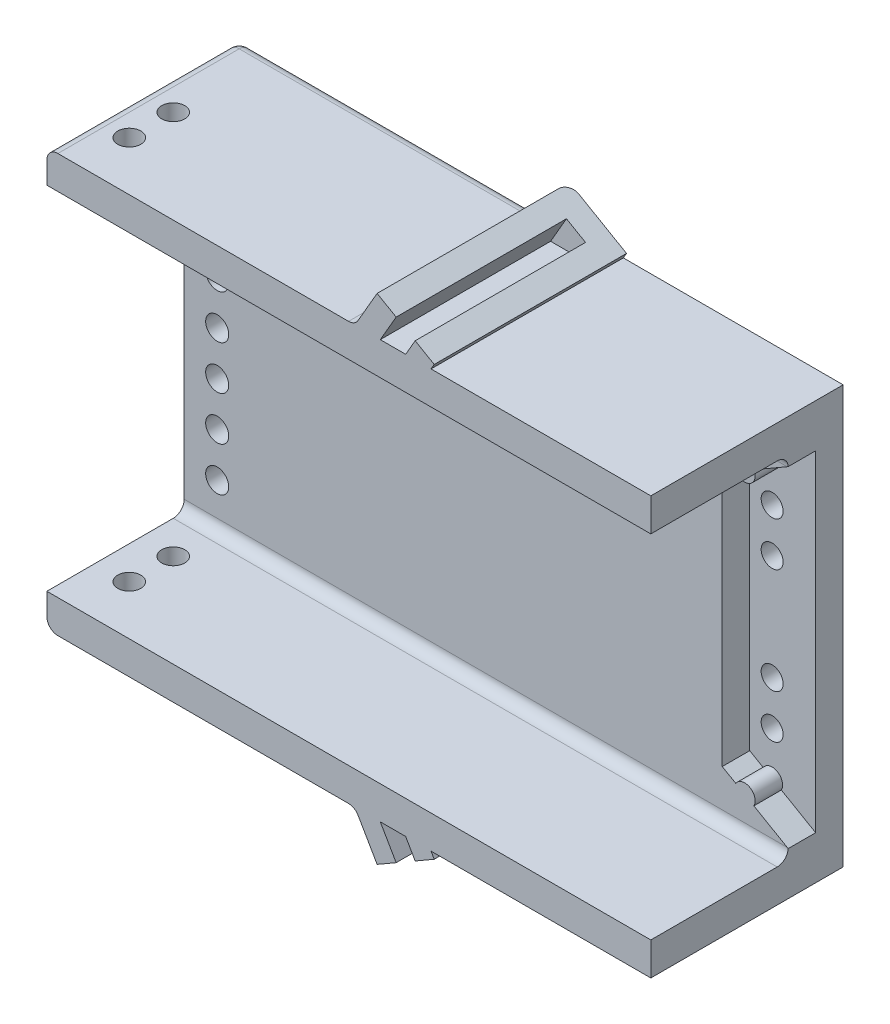
SolidWorks part; units mm, degrees
material "ABS"
ref_plane "前基準面" through (0, 0, 0) normal (0, 0, 1) x (1, 0, 0)
ref_plane "上基準面" through (0, 0, 0) normal (0, 1, 0) x (1, 0, 0)
ref_plane "右基準面" through (0, 0, 0) normal (1, 0, 0) x (0, 0, -1)
sketch "草圖2" plane through (0, 0, 0) normal (0, 0, 1) x (1, 0, 0)
  line L1 (-42.4346, 62.0442) -> (67.4854, 62.0442)
  line L2 (-42.4346, 62.0442) -> (-42.4346, -13.9558)
  line L3 (-42.4346, -13.9558) -> (67.4854, -13.9558)
  line L4 (67.4854, 62.0442) -> (67.4854, -13.9558)
  dimension "D1" = 109.92
  dimension "D2" = 76
extrude "填料-伸長1" add sketch "草圖2" along normal blind 10
sketch "草圖3" plane through (0, 0, 10) normal (0, 0, 1) x (1, 0, 0)
  line L0 (67.4854, 54.1442) -> (67.4854, -6.0558)
  line L1 (67.4854, -13.9558) -> (67.4854, 62.0442) construction
  line L2 (67.4854, 62.0442) -> (-42.4346, 62.0442) construction
  line L3 (67.4854, 54.1442) -> (55.4854, 47.2142)
  line L4 (55.4854, 47.2142) -> (55.4854, 0.8742)
  line L5 (55.4854, 0.8742) -> (67.4854, -6.0558)
  circle A0 centre (59.5654, 49.6442) radius 1.9
  circle A1 centre (59.5654, -1.5558) radius 1.9
  line M6 (67.4854, -13.9558) -> (67.4854, 62.0442)
  dimension "D7" = 7.92
  dimension "D8" = 7.92
  dimension "D9" = 3.8
  dimension "D10" = 3.8
  dimension "D12" = 12.4
  dimension "D1" = 60.2
  dimension "D2" = 7.9
  dimension "D3" = 12
  dimension "D4" = 12
  dimension "D5" = 46.34
  dimension "D6" = 6.93
  dimension "D11" = 51.2
extrude "除料-伸長1" cut sketch "草圖3" against normal blind 5 contours A1 L5 L3 A0 L4 M6
sketch "草圖4" plane through (0, 0, 5) normal (0, 0, 1) x (1, 0, 0)
  line L0 (67.4854, -6.0558) -> (67.4854, 54.1442) construction
  circle A0 centre (59.5654, 41.6442) radius 2
  arc A1 (57.953, 48.6392) -> (61.2418, 50.5385) centre (59.5654, 49.6442) ccw construction
  circle A2 centre (59.5654, 33.6442) radius 2
  circle A3 centre (59.5654, 6.4442) radius 2
  arc A4 (61.2418, -2.4501) -> (57.953, -0.5508) centre (59.5654, -1.5558) ccw construction
  circle A5 centre (59.5654, 14.4442) radius 2
  dimension "D1" = 7.92
  dimension "D2" = 8
  dimension "D3" = 4
  dimension "D5" = 4
  dimension "D6" = 7.92
  dimension "D7" = 8
  dimension "D4" = 2
  dimension "D8" = 2
extrude "除料-伸長2" cut sketch "草圖4" against normal through all
sketch "草圖5" plane through (0, 0, 10) normal (0, 0, 1) x (1, 0, 0)
  line L0 (67.4854, -13.9558) -> (67.4854, -6.0558) construction
  line L1 (-42.4346, -13.9558) -> (67.4854, -13.9558)
  line L2 (-42.4346, -13.9558) -> (-42.4346, -7.9558)
  line L3 (-42.4346, -7.9558) -> (67.4854, -7.9558)
  line L4 (67.4854, -13.9558) -> (67.4854, -7.9558)
  line L5 (-42.4346, 62.0442) -> (-42.4346, -13.9558) construction
  line L6 (67.4854, 62.0442) -> (-42.4346, 62.0442)
  line L7 (67.4854, 62.0442) -> (67.4854, 56.0442)
  line L8 (67.4854, 56.0442) -> (-42.4346, 56.0442)
  line L9 (-42.4346, 62.0442) -> (-42.4346, 56.0442)
  dimension "D1" = 6
  dimension "D2" = 6
extrude "填料-伸長2" add sketch "草圖5" along normal blind 25
sketch "草圖7" plane through (0, -7.9558, 0) normal (0, 1, 0) x (1, 0, 0)
  line L0 (67.4854, -10) -> (-42.4346, -10) construction
  line L1 (-42.4346, -35) -> (-42.4346, -10) construction
  circle A0 centre (-36.4346, -18) radius 2.1
  circle A1 centre (-36.4346, -26) radius 2.1
  dimension "D1" = 4.2
  dimension "D2" = 8
  dimension "D4" = 6
  dimension "D3" = 2
extrude "除料-伸長3" cut sketch "草圖7" against normal through all both and the other way through all
sketch "草圖9" plane through (0, 0, 10) normal (0, 0, 1) x (1, 0, 0)
  line L2 (-42.4346, 56.0442) -> (-42.4346, -7.9558) construction
  line L3 (67.4854, -7.9558) -> (-42.4346, -7.9558) construction
  circle A0 centre (-36.4346, 0.0442) radius 2.1
  circle A1 centre (-36.4346, 8.0442) radius 2.1
  circle A2 centre (-36.4346, 16.0442) radius 2.1
  circle A3 centre (-36.4346, 24.0442) radius 2.1
  circle A4 centre (-36.4346, 32.0442) radius 2.1
  circle A5 centre (-36.4346, 40.0442) radius 2.1
  circle A6 centre (-36.4346, 48.0442) radius 2.1
  dimension "D1" = 6
  dimension "D2" = 4.2
  dimension "D3" = 8
  dimension "D4" = 7
extrude "除料-伸長4" cut sketch "草圖9" against normal through all
sketch "草圖10" plane through (0, 0, 0) normal (0, 0, -1) x (-1, 0, 0)
  line L0 (36.4346, 0.0442) -> (36.4346, 48.0442) construction
  line L1 (32.4346, 0.0442) -> (32.4346, 48.0442)
  line L2 (40.4346, 0.0442) -> (40.4346, 48.0442)
  arc A0 (32.4346, 0.0442) -> (40.4346, 0.0442) centre (36.4346, 0.0442) ccw
  arc A1 (40.4346, 48.0442) -> (32.4346, 48.0442) centre (36.4346, 48.0442) ccw
  point P4 (36.4346, 24.0442)
  dimension "D1" = 8
extrude "除料-伸長5" cut sketch "草圖10" against normal blind 5
sketch "草圖12" plane through (0, 0, 35) normal (0, 0, 1) x (1, 0, 0)
  line L0 (13.629, 62.0442) -> (17.6705, 69.0442)
  line L1 (67.4854, 62.0442) -> (-42.4346, 62.0442) construction
  line L2 (17.6705, 69.0442) -> (28.0628, 63.0442)
  line L3 (28.0628, 63.0442) -> (27.4854, 62.0442)
  line L4 (27.4854, 62.0442) -> (13.629, 62.0442)
  line L5 (22.8666, 62.0442) -> (24.5987, 65.0442)
  line L6 (21.1346, 67.0442) -> (18.2478, 62.0442)
  line L7 (13.629, -13.9558) -> (17.6705, -20.9558)
  line L8 (-42.4346, -13.9558) -> (67.4854, -13.9558) construction
  line L9 (17.6705, -20.9558) -> (28.0628, -14.9558)
  line L10 (28.0628, -14.9558) -> (27.4854, -13.9558)
  line L11 (27.4854, -13.9558) -> (13.629, -13.9558)
  line L12 (24.5987, -16.9558) -> (22.8666, -13.9558)
  line L13 (21.1346, -18.9558) -> (18.2478, -13.9558)
  line M10 (67.4854, 62.0442) -> (-42.4346, 62.0442)
  dimension "D1" = 12
  dimension "D2" = 4
  dimension "D3" = 4
  dimension "D4" = 1
  dimension "D5" = 60
  dimension "D6" = 12
  dimension "D7" = 4
  dimension "D8" = 4
  dimension "D9" = 60
  dimension "D10" = 1
  dimension "D11" = 40
  dimension "D12" = 40
extrude "填料-伸長3" add sketch "草圖12" against normal up to surface (35 mm away) contours L6 L2 L0 M10 | L5 L3 L2 M10 | L12 L9 L10 L11 | L9 L13 L11 L7 up to face at (-36.4346, 24.0442, 0)
fillet "圓角1" radius 2 11 edges at (12.5254, 56.0442, 10) (12.5254, -7.9558, 10) (-42.4346, 62.0442, 17.5) (-42.4346, -13.9558, 17.5) (-42.4346, 24.0442, 0) (-14.4028, -13.9558, 0) (15.6498, -17.4558, 0) (15.6498, 65.5442, 0) (13.629, -13.9558, 17.5) (13.629, 62.0442, 17.5) (-14.4028, 62.0442, 0)
sketch "草圖13" plane through (0, 0, 0) normal (0, 0, -1) x (-1, 0, 0)
  line L0 (-21.1346, -18.9558) -> (-24.5987, -16.9558)
  line L1 (-24.5987, -16.9558) -> (-22.8666, -13.9558)
  line L2 (-22.8666, -13.9558) -> (-18.2478, -13.9558)
  line L3 (-18.2478, -13.9558) -> (-21.1346, -18.9558)
  line L4 (-22.8666, 62.0442) -> (-24.5987, 65.0442)
  line L5 (-24.5987, 65.0442) -> (-21.1346, 67.0442)
  line L6 (-21.1346, 67.0442) -> (-18.2478, 62.0442)
  line L7 (-18.2478, 62.0442) -> (-22.8666, 62.0442)
extrude "填料-伸長4" add sketch "草圖13" against normal blind 4
